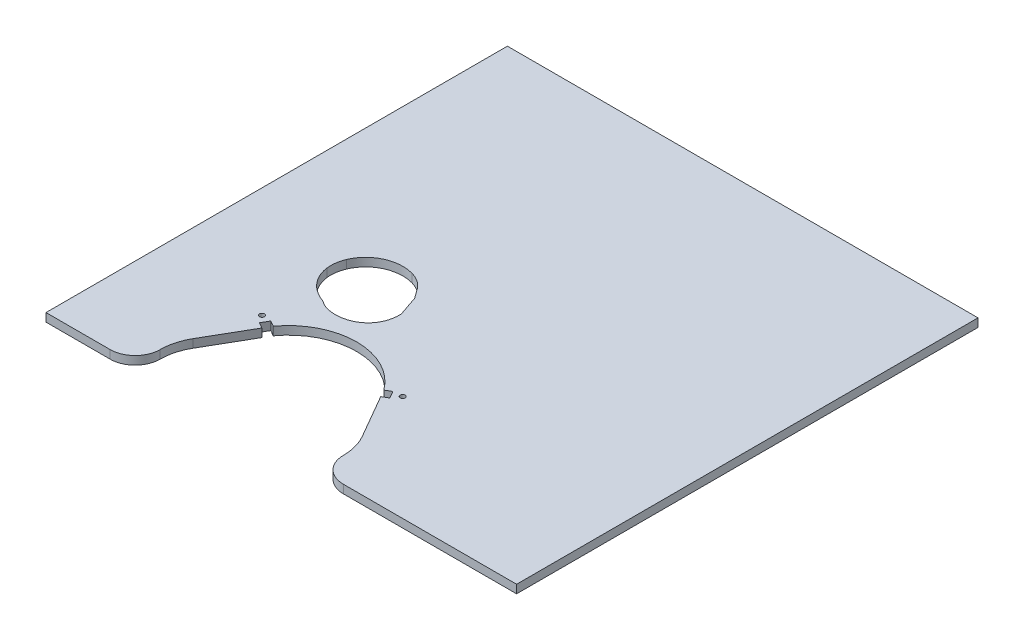
SolidWorks part; units mm, degrees
material "ABS PC"
ref_plane "Plan de face" through (0, 0, 0) normal (0, 0, 1) x (1, 0, 0)
ref_plane "Plan de dessus" through (0, 0, 0) normal (0, 1, 0) x (1, 0, 0)
ref_plane "Plan de droite" through (0, 0, 0) normal (1, 0, 0) x (0, 0, -1)
sketch "Esquisse1" plane through (0, 0, 0) normal (0, 1, 0) x (1, 0, 0)
  line L1 (-140.5, 31.9) -> (141.9979, 31.9)
  line L2 (-140.5, 31.9) -> (-140.5, -245.0829)
  line L3 (-140.5, -245.0829) -> (141.9979, -245.0829)
  line L4 (141.9979, 31.9) -> (141.9979, -245.0829)
  line L5 (38, -245.0829) -> (54.7016, -245.0829) construction
  line L6 (99.5, 31.9) -> (113.5, 31.9) construction
  arc A0 (-32, -23.5) -> (-95.029, -220.3153) centre (-32, -132) ccw construction
extrude "Boss.-Extru.1" add sketch "Esquisse1" along normal blind 5
sketch "Esquisse2" plane through (0, 0, 0) normal (0, 1, 0) x (1, 0, 0)
  line L3 (-65.1815, -184) -> (-68.6457, -182)
  line L4 (-68.6457, -182) -> (-71.1457, -186.3301)
  line L5 (-71.1457, -186.3301) -> (-67.6815, -188.3301)
  line L7 (-32, -132) -> (-32, -245.0829) construction
  line L8 (-65.1815, -184) -> (-67.6815, -188.3301) construction
  line L9 (-62.6323, -132) -> (62.6323, -132) construction
  line L10 (-32, -62.6323) -> (-32, 62.6323) construction
  line L11 (-67.6815, -188.3301) -> (-82.8539, -214.6094)
  line L13 (-65.1815, -184) -> (-61.7174, -186) construction
  line L14 (-32, -168.5125) -> (-32, -231.5125) construction
  line L16 (140.1, -245.0829) -> (-140.1, -245.0829) construction
  line L17 (-140.5, -245.0829) -> (141.9979, -245.0829) construction
  line L18 (1.1815, -184) -> (-2.2826, -186) construction
  line L20 (1.1815, -184) -> (3.6815, -188.3301) construction
  line L21 (3.6815, -188.3301) -> (18.8539, -214.6094)
  line L22 (7.1457, -186.3301) -> (3.6815, -188.3301)
  line L23 (4.6457, -182) -> (7.1457, -186.3301)
  line L24 (1.1815, -184) -> (4.6457, -182)
  line L25 (-69.8957, -184.1651) -> (-74.2258, -181.6651) construction
  line L26 (-102, -245.0829) -> (38, -245.0829)
  arc A1 (1.1815, -184) -> (-65.1815, -184) centre (-32, -208.0829) ccw
  arc A2 (-102, -245.0829) -> (-87, -230.0829) centre (-102, -230.0829) ccw
  arc A3 (-102, -245.0829) -> (-93.2863, -217.8734) centre (-102, -230.0829) ccw construction
  arc A4 (-87, -230.0829) -> (-82.8539, -214.6094) centre (-56.0531, -230.0829) cw
  arc A5 (23, -230.0829) -> (18.8539, -214.6094) centre (-7.9469, -230.0829) ccw
  arc A6 (38, -245.0829) -> (23, -230.0829) centre (38, -230.0829) cw
  circle A8 centre (-74.2258, -181.6651) radius 1.5
  circle A10 centre (10.2258, -181.6651) radius 1.5
  dimension "D4" = 41
  dimension "D8" = 5
  dimension "D9" = 3
  dimension "D1" = 4
  dimension "D2" = 52
  dimension "D3" = 37
  dimension "D5" = 90
  dimension "D6" = 5
  dimension "D7" = 30
extrude "Enlèv. mat.-Extru.2" cut sketch "Esquisse2" along normal through all
sketch "Esquisse3" plane through (0, 5, 0) normal (0, 1, 0) x (1, 0, 0)
  line L0 (-37.2322, -127.0569) -> (-33.1247, -139.1312)
  spline S0 degree 3 poles (-1531.8341, -1452.5331) (-207.5452, -428.348) (3.8704, -188.1918) (-38.7245, -126.6315) (-38.8941, -126.3945) (-39.4016, -125.6823) (-39.7422, -125.2091) (-65.8228, -89.2587) (-97.5389, -57.2295) (-1666.8243, -1285.8652) knots -31.850463 -31.850463 -31.850463 -31.850463 0.125 0.125 0.25 0.25 0.5 0.5 19.29405 19.29405 19.29405 19.29405 only from (-38.0727, -127.5986) to (-42.1803, -121.9365)
  spline S1 degree 3 poles (357.0931, 1835.8687) (-347.6814, -513.038) (-120.9465, -84.5198) (-47.8811, -117.114) (-47.044, -117.5631) (-45.8602, -118.3319) (-45.4767, -118.6044) (-44.7343, -119.185) (-44.3745, -119.4945) (-21.0434, -142.3698) (-75.5996, -233.8683) (1512.3139, 1134.9781) knots -20.904049 -20.904049 -20.904049 -20.904049 0.25 0.25 0.5 0.5 0.625 0.625 0.75 0.75 9.313235 9.313235 9.313235 9.313235 only from (-51.3577, -115.7789) to (-42.1803, -121.9365)
  spline S2 degree 3 poles (-1312.5548, -1643.1059) (1.9079, -543.4216) (23.3671, -122.9167) (-56.4488, -114.9227) (-57.737, -114.9092) (-59.6603, -115.0546) (-60.2999, -115.1309) (-61.576, -115.34) (-62.2153, -115.474) (-64.0956, -115.9555) (-65.3066, -116.3821) (-67.0589, -117.1815) (-67.6325, -117.4741) (-68.7574, -118.1146) (-69.3096, -118.4643) (-70.8985, -119.5739) (-71.8782, -120.402) (-73.225, -121.7806) (-73.6531, -122.2633) (-74.2625, -123.0236) (-74.4604, -123.2834) (-74.8414, -123.8087) (-75.025, -124.075) (-117.7871, -189.31) (228.2262, -459.8979) (1569.8374, -1257.2957) knots -7.457247 -7.457247 -7.457247 -7.457247 0.125 0.125 0.25 0.25 0.3125 0.3125 0.375 0.375 0.5 0.5 0.5625 0.5625 0.625 0.625 0.75 0.75 0.8125 0.8125 0.84375 0.84375 0.875 0.875 8.398041 8.398041 8.398041 8.398041 only from (-51.3577, -115.7789) to (-77, -127.755)
  spline S3 degree 3 poles (-54.9813, 1856.8275) (118.181, -244.0769) (-79.0855, -184.256) (-78.4642, -134.1161) (-78.4011, -133.3001) (-78.1736, -131.6775) (-78.0075, -130.8697) (-24.8642, 63.8002) (2962.019, -622.8948) (-1658.8454, 973.7425) knots -14.76961 -14.76961 -14.76961 -14.76961 0.25 0.25 0.5 0.5 0.75 0.75 62.135828 62.135828 62.135828 62.135828 only from (-78.343, -137.3985) to (-77, -127.755)
  spline S4 degree 3 poles (-2008.2881, 32.8008) (2622.6596, 821.1196) (-132.1007, 42.2047) (-77.5251, -141.1324) (-77.3458, -141.6526) (-76.9413, -142.6832) (-76.718, -143.1876) (-75.9919, -144.665) (-75.4298, -145.6034) (-74.479, -146.9469) (-74.1435, -147.384) (-73.4359, -148.235) (-73.0677, -148.6441) (-71.924, -149.8269) (-71.1096, -150.5562) (-69.7975, -151.5474) (-69.3475, -151.8633) (-68.6568, -152.3195) (-68.425, -152.47) (-67.9583, -152.7645) (-67.7209, -152.9041) (-67.001, -153.3084) (-66.5102, -153.5575) (-65.5114, -154.0234) (-65.0032, -154.2398) (-64.2409, -154.5624) (-63.9867, -154.6699) (-63.4801, -154.8889) (-63.2268, -154.9985) (-62.7258, -155.2315) (-62.4826, -155.3662) (-50.6824, -163.0213) (-51.4169, -201.2221) (718.64, 1684.5228) knots -21.636057 -21.636057 -21.636057 -21.636057 0.125 0.125 0.1875 0.1875 0.25 0.25 0.375 0.375 0.4375 0.4375 0.5 0.5 0.625 0.625 0.6875 0.6875 0.71875 0.71875 0.75 0.75 0.8125 0.8125 0.875 0.875 0.90625 0.90625 0.9375 0.9375 0.96875 0.96875 2.500832 2.500832 2.500832 2.500832 only from (-78.343, -137.3985) to (-61.5478, -156)
  spline S5 degree 3 poles (-1745.4139, 892.0598) (133.9741, 43.0874) (-4.0887, -175.9233) (-59.26, -157.2053) (-59.4819, -157.1257) (-59.8129, -157.0004) (-59.9231, -156.9582) (-60.1393, -156.8624) (-60.2451, -156.8096) (-60.557, -156.6406) (-60.7605, -156.5209) (-73.1987, -148.6858) (-65.0496, -108.9252) (-1170.5294, -1819.9055) knots -30.265211 -30.265211 -30.265211 -30.265211 0.5 0.5 0.625 0.625 0.6875 0.6875 0.75 0.75 0.875 0.875 8.537384 8.537384 8.537384 8.537384 only from (-56.3008, -158) to (-61.5478, -156)
  spline S6 degree 3 poles (-1956.1275, 426.9773) (36.5324, -0.0898) (-5.7039, -154.0463) (-51.2435, -158.3269) (-51.8765, -158.3561) (-53.1445, -158.356) (-53.7811, -158.3264) (-125.6227, -151.5571) (-150.9564, 223.9249) (-22.0957, 1838.9163) knots -17.515041 -17.515041 -17.515041 -17.515041 0.25 0.25 0.5 0.5 0.75 0.75 28.888572 28.888572 28.888572 28.888572 only from (-48.7229, -158) to (-56.3008, -158)
  spline S7 degree 3 poles (-1673.5719, -1296.3963) (-72.6297, 95.6251) (0.8642, -129.1094) (-43.0016, -155.9655) (-43.6799, -156.3213) (-45.0707, -156.9471) (-45.7813, -157.2165) (-93.4686, -172.17) (-208.3678, -13.098) (1705.2684, 789.9411) knots -16.36827 -16.36827 -16.36827 -16.36827 0.25 0.25 0.5 0.5 0.75 0.75 16.93969 16.93969 16.93969 16.93969 only from (-40.4851, -154.245) to (-48.7229, -158)
  spline S8 degree 3 poles (1039.2166, -1823.3231) (-791.0739, 385.5367) (-108.1747, -227.9262) (-38.3895, -152.2364) (-38.1171, -151.9192) (-37.5932, -151.2613) (-37.343, -150.9217) (-36.6368, -149.8847) (-36.2193, -149.1653) (-35.6747, -148.043) (-35.5063, -147.6619) (-22.3248, -114.6524) (-104.8799, -22.7511) (-919.2607, -1937.4947) knots -30.529041 -30.529041 -30.529041 -30.529041 0.25 0.25 0.375 0.375 0.5 0.5 0.75 0.75 0.875 0.875 11.380924 11.380924 11.380924 11.380924 only from (-40.4851, -154.245) to (-34.928, -146.0877)
  spline S9 degree 3 poles (-96.1423, -2133.2638) (-217.1557, -2.8223) (-28.556, -93.2311) (-40.3079, -196.0579) (-269.9799, -213.9602) (-2027.0373, 10.4615) knots -20.97712 -20.97712 -20.97712 -20.97712 0.5 0.5 23.678782 23.678782 23.678782 23.678782 only from (-34.1228, -139.1933) to (-34.928, -146.0877)
  spline S10 degree 3 poles (-34.1228, -139.1933) (-34.0502, -140.3605) (-34.0765, -141.534) (-34.3396, -143.8367) (-34.5752, -144.9715) (-34.928, -146.0877) knots 0 0 0 0 0.5 0.5 1 1 1 1 construction
  spline S11 degree 3 poles (-40.4851, -154.245) (-39.8413, -153.7217) (-39.2363, -153.1548) (-38.3895, -152.2364) (-38.1171, -151.9192) (-37.5932, -151.2613) (-37.343, -150.9217) (-36.6368, -149.8847) (-36.2193, -149.1653) (-35.6747, -148.043) (-35.5063, -147.6619) (-35.1963, -146.8857) (-35.0548, -146.4892) (-34.928, -146.0877) knots 0 0 0 0 0.25 0.25 0.375 0.375 0.5 0.5 0.75 0.75 0.875 0.875 1 1 1 1 construction
  spline S12 degree 3 poles (-40.4851, -154.245) (-41.0776, -154.7266) (-41.7013, -155.1695) (-43.0016, -155.9655) (-43.6799, -156.3213) (-45.0707, -156.9471) (-45.7813, -157.2165) (-47.2317, -157.6713) (-47.9731, -157.8572) (-48.7229, -158) knots 0 0 0 0 0.25 0.25 0.5 0.5 0.75 0.75 1 1 1 1 construction
  spline S13 degree 3 poles (-48.7229, -158) (-49.3482, -158.1191) (-49.9796, -158.2081) (-51.2435, -158.3269) (-51.8765, -158.3561) (-53.1445, -158.356) (-53.7811, -158.3264) (-55.0464, -158.2072) (-55.6755, -158.1184) (-56.3008, -158) knots 0 0 0 0 0.25 0.25 0.5 0.5 0.75 0.75 1 1 1 1 construction
  spline S14 degree 3 poles (-56.3008, -158) (-57.2287, -157.8243) (-58.1437, -157.584) (-59.26, -157.2053) (-59.4819, -157.1257) (-59.8129, -157.0004) (-59.9231, -156.9582) (-60.1393, -156.8624) (-60.2451, -156.8096) (-60.557, -156.6406) (-60.7605, -156.5209) (-61.1598, -156.2694) (-61.3541, -156.1351) (-61.5478, -156) knots 0 0 0 0 0.5 0.5 0.625 0.625 0.6875 0.6875 0.75 0.75 0.875 0.875 1 1 1 1 construction
  spline S15 degree 3 poles (-78.343, -137.3985) (-78.2139, -138.4875) (-77.994, -139.5573) (-77.5251, -141.1324) (-77.3458, -141.6526) (-76.9413, -142.6832) (-76.718, -143.1876) (-75.9919, -144.665) (-75.4298, -145.6034) (-74.479, -146.9469) (-74.1435, -147.384) (-73.4359, -148.235) (-73.0677, -148.6441) (-71.924, -149.8269) (-71.1096, -150.5562) (-69.7975, -151.5474) (-69.3475, -151.8633) (-68.6568, -152.3195) (-68.425, -152.47) (-67.9583, -152.7645) (-67.7209, -152.9041) (-67.001, -153.3084) (-66.5102, -153.5575) (-65.5114, -154.0234) (-65.0032, -154.2398) (-64.2409, -154.5624) (-63.9867, -154.6699) (-63.4801, -154.8889) (-63.2268, -154.9985) (-62.7258, -155.2315) (-62.4826, -155.3662) (-62.0108, -155.6722) (-61.7801, -155.838) (-61.5478, -156) knots 0 0 0 0 0.125 0.125 0.1875 0.1875 0.25 0.25 0.375 0.375 0.4375 0.4375 0.5 0.5 0.625 0.625 0.6875 0.6875 0.71875 0.71875 0.75 0.75 0.8125 0.8125 0.875 0.875 0.90625 0.90625 0.9375 0.9375 0.96875 0.96875 1 1 1 1 construction
  spline S16 degree 3 poles (-78.343, -137.3985) (-78.4399, -136.5817) (-78.4845, -135.7579) (-78.4642, -134.1161) (-78.4011, -133.3001) (-78.1736, -131.6775) (-78.0075, -130.8697) (-77.5764, -129.2906) (-77.3122, -128.5156) (-77, -127.755) knots 0 0 0 0 0.25 0.25 0.5 0.5 0.75 0.75 1 1 1 1 construction
  spline S17 degree 3 poles (-51.3577, -115.7789) (-52.5925, -115.4238) (-53.8598, -115.182) (-56.4488, -114.9227) (-57.737, -114.9092) (-59.6603, -115.0546) (-60.2999, -115.1309) (-61.576, -115.34) (-62.2153, -115.474) (-64.0956, -115.9555) (-65.3066, -116.3821) (-67.0589, -117.1815) (-67.6325, -117.4741) (-68.7574, -118.1146) (-69.3096, -118.4643) (-70.8985, -119.5739) (-71.8782, -120.402) (-73.225, -121.7806) (-73.6531, -122.2633) (-74.2625, -123.0236) (-74.4604, -123.2834) (-74.8414, -123.8087) (-75.025, -124.075) (-75.9095, -125.4243) (-76.5098, -126.5605) (-77, -127.755) knots 0 0 0 0 0.125 0.125 0.25 0.25 0.3125 0.3125 0.375 0.375 0.5 0.5 0.5625 0.5625 0.625 0.625 0.75 0.75 0.8125 0.8125 0.84375 0.84375 0.875 0.875 1 1 1 1 construction
  spline S18 degree 3 poles (-51.3577, -115.7789) (-50.4629, -116.0363) (-49.5879, -116.3526) (-47.8811, -117.114) (-47.044, -117.5631) (-45.8602, -118.3319) (-45.4767, -118.6044) (-44.7343, -119.185) (-44.3745, -119.4945) (-43.3675, -120.4818) (-42.7623, -121.1988) (-42.1803, -121.9365) knots 0 0 0 0 0.25 0.25 0.5 0.5 0.625 0.625 0.75 0.75 1 1 1 1 construction
  spline S19 degree 3 poles (-38.0727, -127.5986) (-38.2308, -127.3534) (-38.3928, -127.111) (-38.7245, -126.6315) (-38.8941, -126.3945) (-39.4016, -125.6823) (-39.7422, -125.2091) (-40.7693, -123.7933) (-41.4583, -122.8518) (-42.1803, -121.9365) knots 0 0 0 0 0.125 0.125 0.25 0.25 0.5 0.5 1 1 1 1 construction
  spline S20 degree 1 poles (-33.1247, -139.1312) (-33.9745, -146.389) knots 0 0 1 1 construction
  spline S21 degree 1 poles (-39.8544, -155.021) (-33.9745, -146.389) knots 0 0 1 1 construction
  spline S22 degree 1 poles (-39.8544, -155.021) (-48.5359, -158.9824) knots 0 0 1 1 construction
  spline S23 degree 1 poles (-48.5359, -158.9824) (-56.4869, -158.9825) knots 0 0 1 1 construction
  spline S24 degree 1 poles (-56.4869, -158.9825) (-62.1198, -156.8203) knots 0 0 1 1 construction
  spline S25 degree 1 poles (-79.336, -137.5162) (-62.1198, -156.8203) knots 0 0 1 1 construction
  spline S26 degree 1 poles (-79.336, -137.5162) (-77.9251, -127.3753) knots 0 0 1 1 construction
  spline S27 degree 1 poles (-51.0813, -114.8179) (-77.9251, -127.3753) knots 0 0 1 1 construction
  spline S28 degree 1 poles (-51.0813, -114.8179) (-41.3952, -121.3172) knots 0 0 1 1 construction
  spline S29 degree 1 poles (-37.2322, -127.0569) (-41.3952, -121.3172) knots 0 0 1 1 construction
  spline S30 degree 3 poles (-33.1247, -139.1312) (-32.9734, -141.5623) (-33.2405, -144.0664) (-33.9745, -146.389) knots 0 0 0 0 1 1 1 1
  spline S31 degree 3 poles (-33.9745, -146.389) (-34.2409, -147.2323) (-34.9017, -148.8872) (-36.2221, -151.1686) (-37.8961, -153.272) (-39.1739, -154.4679) (-39.8544, -155.021) knots 0 0 0 0 0.25 0.5 0.75 1 1 1 1
  spline S32 degree 3 poles (-39.8544, -155.021) (-41.1022, -156.0352) (-43.8953, -157.7328) (-46.967, -158.6836) (-48.5359, -158.9824) knots 0 0 0 0 0.5 1 1 1 1
  spline S33 degree 3 poles (-48.5359, -158.9824) (-51.1394, -159.4781) (-53.8829, -159.4757) (-56.4869, -158.9825) knots 0 0 0 0 1 1 1 1
  spline S34 degree 3 poles (-56.4869, -158.9825) (-56.9734, -158.8904) (-57.9415, -158.6718) (-59.0056, -158.3522) (-59.7107, -158.1061) (-60.0491, -157.981) (-60.4323, -157.8343) (-60.8396, -157.6291) (-61.1621, -157.4443) (-61.4936, -157.2441) (-61.8226, -157.0271) (-62.0192, -156.8904) (-62.1198, -156.8203) knots 0 0 0 0 0.25 0.5 0.5625 0.625 0.6875 0.75 0.8125 0.875 0.9375 1 1 1 1
  spline S35 degree 3 poles (-62.1198, -156.8203) (-62.3426, -156.6649) (-62.8212, -156.3208) (-63.3578, -156.0288) (-64.1358, -155.6943) (-65.1278, -155.2724) (-66.4415, -154.7137) (-67.7152, -154.07) (-68.7361, -153.4634) (-69.6711, -152.8531) (-71.3255, -151.7044) (-73.4613, -149.7979) (-75.6889, -147.1234) (-78.0457, -143.1846) (-79.0656, -139.797) (-79.336, -137.5162) knots 0 0 0 0 0.03125 0.0625 0.09375 0.125 0.1875 0.25 0.28125 0.3125 0.375 0.5 0.625 0.75 1 1 1 1
  spline S36 degree 3 poles (-79.336, -137.5162) (-79.5389, -135.806) (-79.4971, -132.3145) (-78.5776, -128.965) (-77.9251, -127.3753) knots 0 0 0 0 0.5 1 1 1 1
  spline S37 degree 3 poles (-77.9251, -127.3753) (-77.4131, -126.1277) (-76.1525, -123.7337) (-73.5762, -120.5203) (-70.4912, -117.9189) (-66.9299, -115.8897) (-63.1282, -114.5536) (-59.0981, -113.8904) (-55.0468, -113.9388) (-52.3772, -114.4451) (-51.0813, -114.8179) knots 0 0 0 0 0.125 0.25 0.375 0.5 0.625 0.75 0.875 1 1 1 1
  spline S38 degree 3 poles (-51.0813, -114.8179) (-50.1424, -115.0879) (-48.3106, -115.748) (-46.1035, -116.9336) (-44.4821, -118.0811) (-43.3107, -119.0968) (-42.3076, -120.1888) (-41.6959, -120.936) (-41.3952, -121.3172) knots 0 0 0 0 0.25 0.5 0.625 0.75 0.875 1 1 1 1
  spline S39 degree 3 poles (-41.3952, -121.3172) (-40.6647, -122.2432) (-39.6101, -123.6823) (-38.2535, -125.565) (-37.5565, -126.5538) (-37.2322, -127.0569) knots 0 0 0 0 0.5 0.75 1 1 1 1
  dimension "D1" = 1
extrude "Enlèv. mat.-Extru.3" cut sketch "Esquisse3" against normal through all
